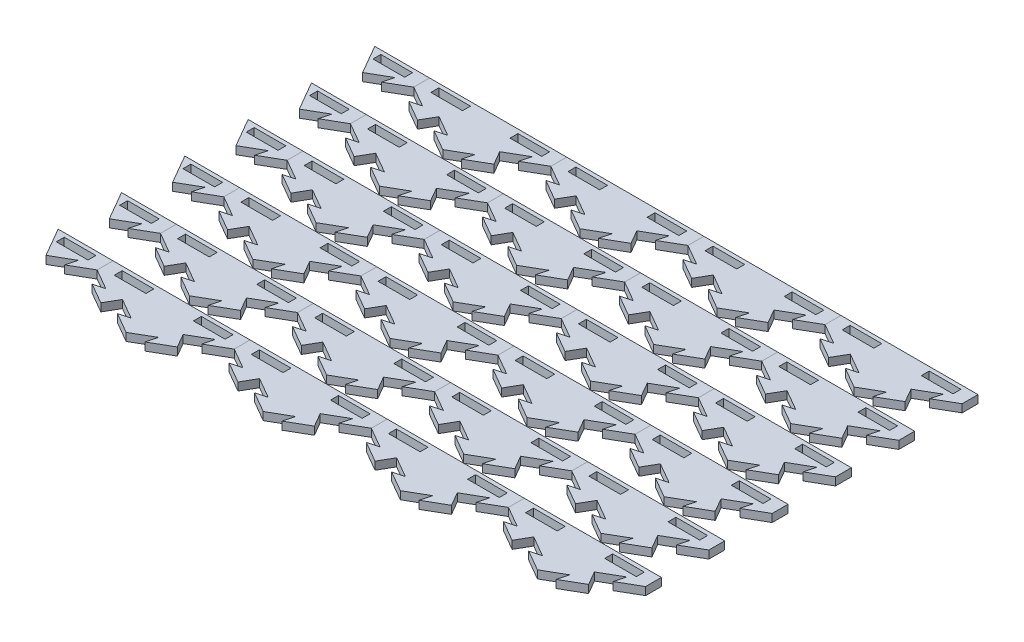
SolidWorks part; units mm, degrees
material "Cedar"
ref_plane "Front Plane" through (0, 0, 0) normal (0, 0, 1) x (1, 0, 0)
ref_plane "Top Plane" through (0, 0, 0) normal (0, 1, 0) x (1, 0, 0)
ref_plane "Right Plane" through (0, 0, 0) normal (1, 0, 0) x (0, 0, -1)
sketch "Sketch1" plane through (0, 0, 0) normal (0, 1, 0) x (1, 0, 0)
  line L0 (-54.9926, 0) -> (54.9926, 0) construction
  line L1 (-54.9926, 0) -> (0, -31.75)
  line L2 (0, -31.75) -> (54.9926, 0)
  line L3 (54.9926, 0) -> (54.9926, 63.5)
  line L4 (54.9926, 63.5) -> (0, 95.25)
  line L5 (0, 95.25) -> (-54.9926, 63.5)
  line L6 (-54.9926, 63.5) -> (-54.9926, 0)
  line L7 (0, -31.75) -> (0, 31.75) construction
  circle A0 centre (0, 31.75) radius 54.9926 construction
  point P9 (0, 0)
  dimension "D1" = 63.5
extrude "Boss-Extrude1" add sketch "Sketch1" against normal blind 6.35
sketch "Sketch2" plane through (0, 0, 0) normal (0, 1, 0) x (1, 0, 0)
  line L0 (-54.9926, 31.75) -> (54.9926, 31.75) construction
  line L1 (-54.9926, 63.5) -> (-54.9926, 0) construction
  line L2 (54.9926, 0) -> (54.9926, 63.5) construction
  point P2 (0, 31.75)
ref_axis "Axis1" through (0, 0, -31.75) along (0, 1, 0)
sketch "Sketch10" plane through (0, 0, 0) normal (0, 1, 0) x (1, 0, 0)
  line L0 (0, -31.75) -> (-16.4978, -22.225) construction
  line L1 (-16.4978, -22.225) -> (-7.8235, -19.9007)
  line L2 (-7.8235, -19.9007) -> (-24.3213, -10.3757)
  line L3 (-24.3213, -10.3757) -> (-27.4963, -15.875)
  line L4 (-16.4978, -22.225) -> (-27.4963, -15.875)
  line L5 (-54.9926, 0) -> (0, -31.75) construction
  dimension "D1" = 45
  dimension "D2" = 6.35
extrude "Cut-Extrude4" cut sketch "Sketch10" against normal through all
sketch "Sketch11" plane through (0, 0, 0) normal (0, 1, 0) x (1, 0, 0)
  line L0 (-27.4963, -15.875) -> (-54.9926, 0) construction
  line L1 (-27.4963, -15.875) -> (-30.6713, -21.3743)
  line L2 (-30.6713, -21.3743) -> (-47.1691, -11.8493)
  line L3 (-47.1691, -11.8493) -> (-38.4948, -9.525)
  line L4 (-38.4948, -9.525) -> (-27.4963, -15.875)
  line L5 (-38.4948, -9.525) -> (-54.9926, 0) construction
  line L6 (-38.4948, -9.525) -> (-54.9926, 0) construction
  line L7 (-54.9926, 0) -> (-27.4963, -15.875) construction
  line L8 (-54.9926, 63.5) -> (-54.9926, 0) construction
  dimension "D1" = 45
  dimension "D2" = 6.35
extrude "Boss-Extrude4" add sketch "Sketch11" against normal blind 6.35
pattern_circular "CirPattern1" count 2 every 60 about axis through (0, 0, -31.75) along (0, 1, 0) of "Cut-Extrude4", "Boss-Extrude4"
sketch "Sketch12" plane through (0, 0, 0) normal (0, 1, 0) x (1, 0, 0)
  line L0 (-54.9926, 12.7) -> (54.9926, 12.7)
  line L1 (-54.9926, 63.5) -> (-54.9926, 0) construction
  line L2 (54.9926, 0) -> (54.9926, 63.5) construction
  line L3 (54.9926, 12.7) -> (54.9926, 95.25)
  line L4 (54.9926, 95.25) -> (-54.9926, 95.25)
  line L5 (-54.9926, 95.25) -> (-54.9926, 12.7)
  line L6 (0, 0) -> (0, 12.7) construction
  dimension "D1" = 12.7
extrude "Cut-Extrude5" cut sketch "Sketch12" against normal through all
sketch "Sketch13" plane through (0, 0, 0) normal (0, 1, 0) x (1, 0, 0)
  line L0 (0, 0) -> (0, 12.7) construction
  line L1 (-54.9926, 12.7) -> (54.9926, 12.7) construction
  line L2 (-31.75, 6.35) -> (31.75, 6.35) construction
  line L4 (-44.45, 9.525) -> (-19.05, 9.525)
  line L5 (-44.45, 9.525) -> (-44.45, 3.175)
  line L6 (-44.45, 3.175) -> (-19.05, 3.175)
  line L7 (-19.05, 9.525) -> (-19.05, 3.175)
  line L8 (-44.45, 9.525) -> (-19.05, 3.175) construction
  line L9 (-44.45, 3.175) -> (-19.05, 9.525) construction
  line L10 (19.05, 9.525) -> (44.45, 9.525)
  line L11 (19.05, 9.525) -> (19.05, 3.175)
  line L12 (19.05, 3.175) -> (44.45, 3.175)
  line L13 (44.45, 9.525) -> (44.45, 3.175)
  line L14 (19.05, 9.525) -> (44.45, 3.175) construction
  line L15 (19.05, 3.175) -> (44.45, 9.525) construction
  point P7 (0, 6.35)
  point P8 (0, 6.35)
  dimension "D1" = 6.35
  dimension "D2" = 25.4
  dimension "D3" = 6.35
  dimension "D4" = 25.4
  dimension "D5" = 63.5
extrude "Cut-Extrude6" cut sketch "Sketch13" against normal through all
pattern_linear "LPattern1" count 5 spacing 109.9852 along (1, 0, 0) count 2 spacing 109.9852 along (-1, 0, 0) pattern seed only yes of bodies 136 131
sketch "Sketch14" plane through (0, 0, 0) normal (0, 1, 0) x (1, 0, 0)
  line L0 (439.9409, -31.75) -> (439.9409, 12.7)
  line L1 (384.9483, 12.7) -> (494.9335, 12.7) construction
  line L2 (439.9409, 12.7) -> (494.9335, 12.7)
  line L3 (494.9335, 12.7) -> (494.9335, -31.75)
  line L4 (494.9335, -31.75) -> (439.9409, -31.75)
  line L5 (-109.9852, -31.75) -> (-109.9852, 12.7)
  line L6 (-164.9778, 12.7) -> (-54.9926, 12.7) construction
  line L7 (-109.9852, 12.7) -> (-164.9778, 12.7)
  line L8 (-164.9778, 12.7) -> (-164.9778, -31.75)
  line L9 (-164.9778, -31.75) -> (-109.9852, -31.75)
  line L10 (415.6196, -10.3757) -> (428.9424, 12.7)
  line L11 (428.9424, 12.7) -> (439.9409, 12.7)
  line L12 (415.6196, -10.3757) -> (409.2696, -21.3743)
  line L13 (409.2696, -21.3743) -> (439.9409, -31.75)
  line L14 (-79.3139, -21.3743) -> (-98.9867, 12.7)
  line L15 (-98.9867, 12.7) -> (-109.9852, 12.7)
  line L16 (-79.3139, -21.3743) -> (-95.8117, -30.8993)
  line L17 (-95.8117, -30.8993) -> (-109.9852, -31.75)
  line L18 (-85.6639, -10.3757) -> (-79.3139, -21.3743) construction
  line M5 (484.3909, 9.525) -> (484.3909, 3.175)
  line M6 (484.3909, 3.175) -> (458.9909, 3.175)
  line M7 (458.9909, 3.175) -> (458.9909, 9.525)
  line M8 (458.9909, 9.525) -> (484.3909, 9.525)
  line M13 (494.9335, 12.7) -> (384.9483, 12.7)
  line M19 (415.6196, -10.3757) -> (432.1174, -19.9007)
  line M20 (432.1174, -19.9007) -> (423.4431, -22.225)
  line M21 (423.4431, -22.225) -> (439.9409, -31.75)
  line M22 (439.9409, -31.75) -> (456.4387, -22.225)
  line M23 (456.4387, -22.225) -> (454.1144, -30.8993)
  line M24 (454.1144, -30.8993) -> (470.6122, -21.3743)
  line M25 (470.6122, -21.3743) -> (464.2622, -10.3757)
  line M26 (464.2622, -10.3757) -> (480.76, -0.8507)
  line M27 (480.76, -0.8507) -> (478.4357, -9.525)
  line M28 (478.4357, -9.525) -> (494.9335, 0)
  line M29 (494.9335, 0) -> (494.9335, 12.7)
extrude "Cut-Extrude7" cut sketch "Sketch14" against normal through all contours L17 L16 L14 L15 L5 | L10 L0 M19 M20 M21 M13 | L0 M22 M23 M24 M25 M26 M27 M28 M29 M13 M8 M5 M6 M7 | L8 L9 L5 L7 region at (431.3731, 0, 7.3494) region at (460.5225, 0, 5.1278) region at (-137.4815, 0, 9.525) region at (-98.715, 0, 11.4335)
sketch "Sketch15" plane through (0, 0, 0) normal (0, 1, 0) x (1, 0, 0)
  line L0 (384.9483, 12.7) -> (428.9424, 12.7)
  line L1 (428.9424, 12.7) -> (428.9424, -21.3743)
  line L2 (428.9424, -21.3743) -> (384.9483, -21.3743)
  line L3 (384.9483, -21.3743) -> (384.9483, 12.7)
extrude "Cut-Extrude8" cut sketch "Sketch15" against normal through all
pattern_linear "LPattern2" count 6 spacing 50.8 along (0, 0, 1) of bodies 145 136 132 133 134
